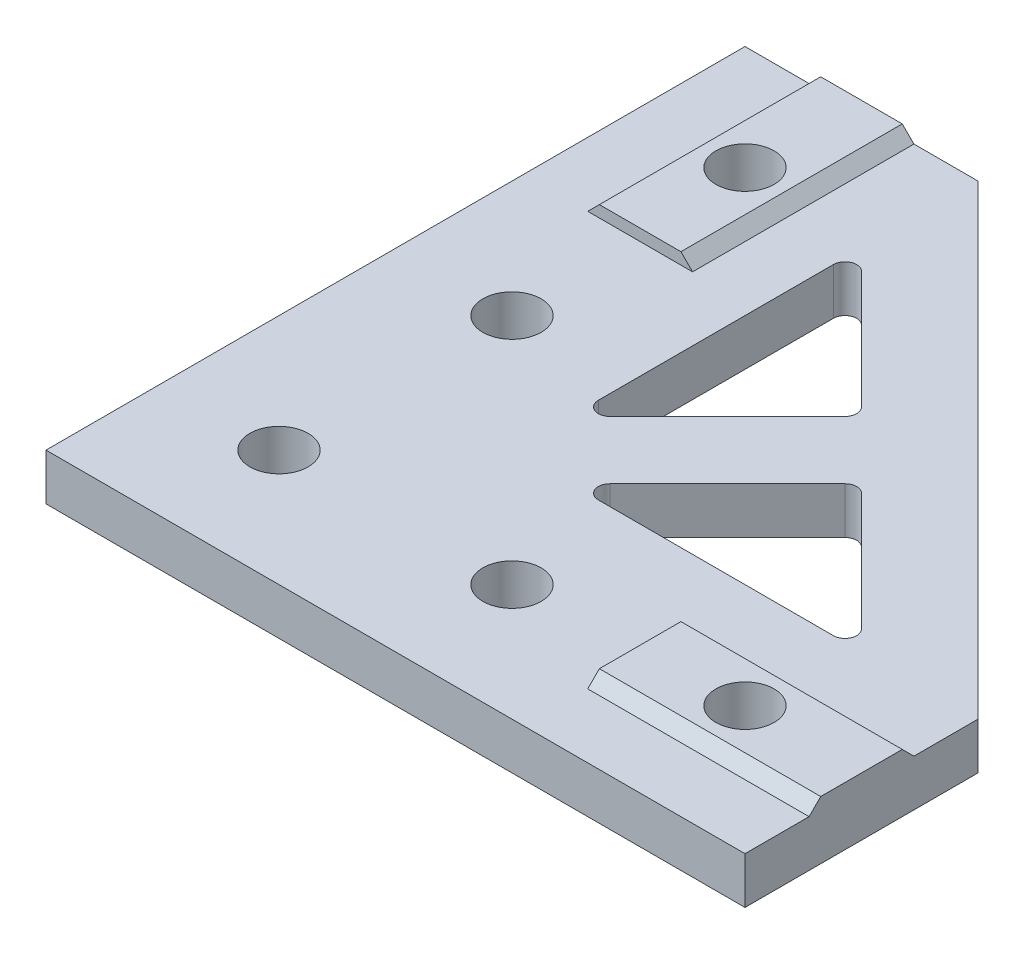
SolidWorks part; units mm, degrees
ref_plane "Front Plane" through (0, 0, 0) normal (0, 0, 1) x (1, 0, 0)
ref_plane "Top Plane" through (0, 0, 0) normal (0, 1, 0) x (1, 0, 0)
ref_plane "Right Plane" through (0, 0, 0) normal (1, 0, 0) x (0, 0, -1)
sketch "Sketch1" plane through (0, 0, 0) normal (0, 1, 0) x (1, 0, 0)
  line L0 (0, 0) -> (0, 60)
  line L1 (0, 0) -> (60, 0)
  line L2 (60, 0) -> (60, 20)
  line L3 (60, 20) -> (20, 60)
  line L4 (20, 60) -> (0, 60)
  point P3 (60, 19.7934)
  dimension "D1" = 20
  dimension "D2" = 60
  dimension "D3" = 60
  dimension "D4" = 20
extrude "Boss-Extrude1" add sketch "Sketch1" along normal blind 4
sketch "Sketch3" plane through (0, 4, 0) normal (0, 1, 0) x (1, 0, 0)
  line L0 (20, 60) -> (0, 60) construction
  line L1 (14.5, 60) -> (5.5, 60)
  line L2 (14.5, 60) -> (14.5, 41)
  line L3 (14.5, 41) -> (5.5, 41)
  line L4 (5.5, 60) -> (5.5, 41)
  line L5 (60, 0) -> (60, 20) construction
  line L6 (60, 5.5) -> (41, 5.5)
  line L7 (60, 5.5) -> (60, 14.5)
  line L8 (60, 14.5) -> (41, 14.5)
  line L9 (41, 5.5) -> (41, 14.5)
  line L10 (0, 60) -> (0, 0) construction
  line L11 (0, 0) -> (60, 0) construction
  dimension "D1" = 9
  dimension "D2" = 9
  dimension "D3" = 19
  dimension "D4" = 19
  dimension "D5" = 5.5
  dimension "D6" = 5.5
extrude "Boss-Extrude2" add sketch "Sketch3" along normal blind 1
chamfer "Chamfer1" distance 1 angle 45 4 edges at (50.5, 5, -14.5) (50.5, 5, -5.5) (14.5, 5, -50.5) (5.5, 5, -50.5)
sketch "Sketch2" plane through (0, 0, 0) normal (0, -1, 0) x (1, 0, 0)
  line L0 (0, 0) -> (60, 0) construction
  line L1 (0, -60) -> (0, 0) construction
  line L2 (20, -60) -> (0, -60) construction
  line L3 (60, 0) -> (60, -20) construction
  line L4 (48.293, -21.7071) -> (38.2071, -31.793)
  line L5 (36.7929, -31.793) -> (26.7071, -21.7071)
  line L6 (27.4142, -20) -> (47.5859, -20)
  line L7 (31.793, -36.7929) -> (21.7071, -26.7071)
  line L8 (20, -27.4142) -> (20, -47.5859)
  line L9 (21.7071, -48.293) -> (31.793, -38.2071)
  line L10 (60, -20) -> (20, -60) construction
  circle A0 centre (50, -10) radius 2.5
  circle A1 centre (30, -10) radius 2.5
  circle A2 centre (10, -10) radius 2.5
  circle A3 centre (10, -30) radius 2.5
  circle A4 centre (10, -50) radius 2.5
  arc A5 (48.293, -21.7071) -> (47.5859, -20) centre (47.5859, -21) ccw
  arc A6 (26.7071, -21.7071) -> (27.4142, -20) centre (27.4142, -21) cw
  arc A7 (38.2071, -31.793) -> (36.7929, -31.793) centre (37.5, -31.0859) cw
  arc A8 (31.793, -36.7929) -> (31.793, -38.2071) centre (31.0859, -37.5) cw
  arc A9 (20, -47.5859) -> (21.7071, -48.293) centre (21, -47.5859) ccw
  arc A10 (21.7071, -26.7071) -> (20, -27.4142) centre (21, -27.4142) ccw
  dimension "D1" = 5
  dimension "D2" = 5
  dimension "D3" = 5
  dimension "D4" = 5
  dimension "D5" = 5
  dimension "D6" = 10
  dimension "D7" = 10
  dimension "D9" = 10
  dimension "D10" = 20
  dimension "D11" = 10
  dimension "D17" = 1
  dimension "D8" = 20
  dimension "D12" = 20
  dimension "D13" = 20
  dimension "D14" = 7.071
  dimension "D15" = 7.071
  dimension "D16" = 7.071
extrude "Cut-Extrude1" cut sketch "Sketch2" against normal through all and the other way through all
